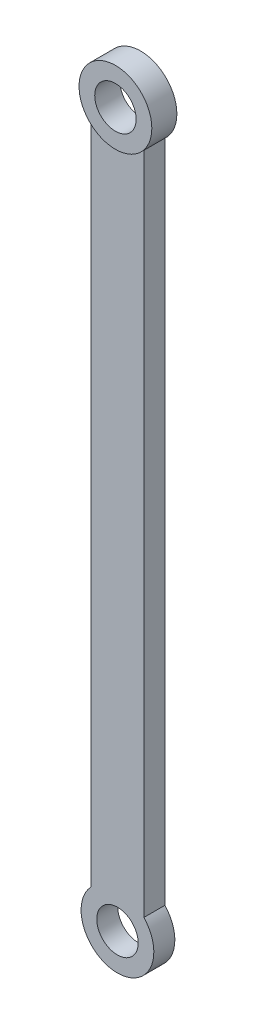
SolidWorks part; units mm, degrees
note: The reader was unsure of these and kept them because the rebuilt part matched: shared geometry of "Croquis1<3>".
ref_plane "Alzado" through (0, 0, 0) normal (0, 0, 1) x (1, 0, 0)
ref_plane "Planta" through (0, 0, 0) normal (0, 1, 0) x (1, 0, 0)
ref_plane "Vista lateral" through (0, 0, 0) normal (1, 0, 0) x (0, 0, -1)
sketch "Croquis1" plane through (0, 0, 0) normal (0, 0, 1) x (1, 0, 0)
  line L0 (0, 0) -> (0, -176.75) construction
  line L3 (-6.54, -6.1829) -> (-6.54, -170.5671)
  line L5 (6.54, -6.1829) -> (6.54, -170.5671)
  circle A0 centre (0, 0) radius 5.125
  circle A1 centre (0, 0) radius 9
  circle A2 centre (0, -176.75) radius 5.125
  circle A3 centre (0, -176.75) radius 9
  dimension "D1" = 10.25
  dimension "D2" = 18
  dimension "D4" = 18
  dimension "D5" = 10.25
  dimension "D3" = 176.75
  dimension "D6" = 13.08
  dimension "D7" = 170.5671
  dimension "D8" = 164.3842
extrude "Saliente-Extruir1" add sketch "Croquis1" along normal mid plane 5.2 contours A1 L0 A3 L5 | L0 A1 L3 A3 | A2
extrude "Saliente-Extruir2" add sketch "Croquis1<3>" along normal mid plane 6.2
sketch "Croquis1<3>" plane through (0, 0, 0) normal (0, 0, 1) x (1, 0, 0) same geometry as "Croquis1"
